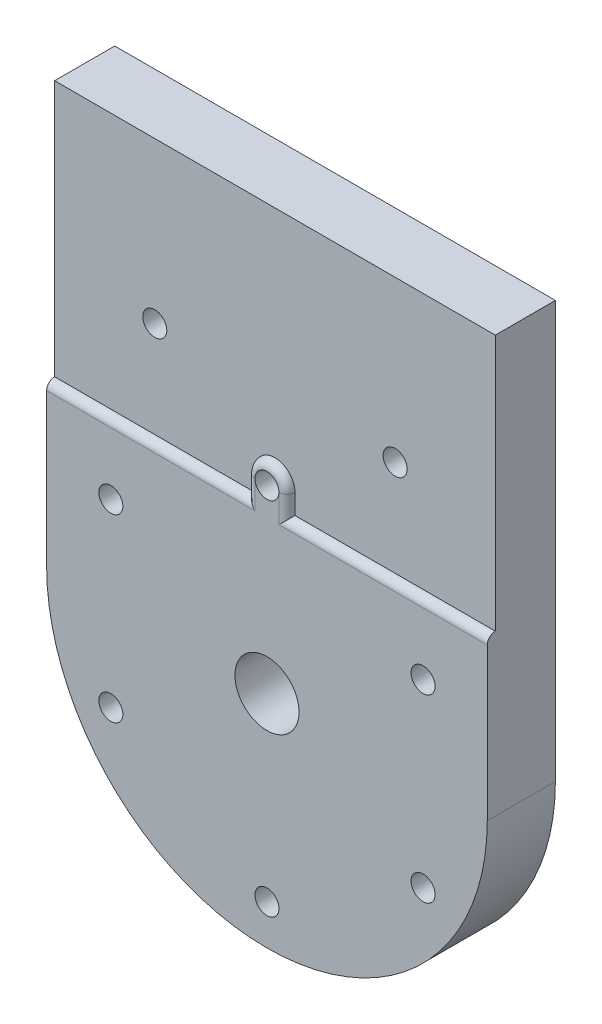
SolidWorks part; units mm, degrees
ref_plane "Plan de face" through (0, 0, 0) normal (0, 0, 1) x (1, 0, 0)
ref_plane "Plan de dessus" through (0, 0, 0) normal (0, 1, 0) x (1, 0, 0)
ref_plane "Plan de droite" through (0, 0, 0) normal (1, 0, 0) x (0, 0, -1)
sketch "Esquisse1" plane through (0, 0, 0) normal (0, 0, 1) x (1, 0, 0)
  line L0 (-50, 52) -> (50, 52)
  line L1 (-50, 52) -> (-50, -48.5481)
  line L2 (50, 52) -> (50, -48.5481)
  line L3 (-50, -48.5481) -> (50, -48.5481)
  circle A1 centre (0, 0) radius 4
  dimension "D1" = 52
extrude "Boss.-Extru.1" add sketch "Esquisse1" along normal blind 8.5
sketch "Esquisse2" plane through (0, 0, 8.5) normal (0, 0, 1) x (1, 0, 0)
  line L0 (-27.5, 0) -> (27.5, 0)
  line L1 (-27.5, 0) -> (-27.5, 55)
  line L2 (27.5, 0) -> (27.5, 55)
  line L3 (-27.5, 55) -> (27.5, 55)
  line L4 (-50, 52) -> (50, 52) construction
  circle A0 centre (0, 22.5) radius 1.5
  circle A1 centre (19.4856, 11.25) radius 1.5
  circle A2 centre (19.4856, -11.25) radius 1.5
  circle A3 centre (0, -22.5) radius 1.5
  circle A4 centre (-19.4856, -11.25) radius 1.5
  circle A5 centre (-19.4856, 11.25) radius 1.5
  circle A6 centre (0, 0) radius 27.5
  circle A13 centre (-15, 32) radius 1.5
  circle A14 centre (15, 32) radius 1.5
  point P4 (0, 0)
  point P12 (0, 0)
  point P32 (0, 0)
  point P33 (0, 0)
  dimension "D1" = 22.5
  dimension "D3" = 55
  dimension "D4" = 55
  dimension "D8" = 12.5
  dimension "D9" = 12.5
  dimension "D10" = 20
  dimension "D11" = 20
  dimension "D2" = 6
extrude "Enlèv. mat.-Extru.1" cut sketch "Esquisse2" against normal through all
sketch "Esquisse3" plane through (0, 0, 8.5) normal (0, 0, 1) x (1, 0, 0)
  line L0 (-27.5, 52) -> (27.5, 52)
  line L1 (-27.5, 52) -> (-27.5, 20)
  line L2 (27.5, 52) -> (27.5, 20)
  line L3 (-27.5, 20) -> (27.5, 20)
  line L4 (-2.5, 20) -> (2.5, 20)
  line L5 (-2.5, 20) -> (-2.5, 22.5)
  line L6 (2.5, 20) -> (2.5, 22.5)
  line L7 (-2.5, 22.5) -> (2.5, 22.5)
  circle A0 centre (0, 22.5) radius 2.5
  circle M14 centre (-15, 32) radius 1.5
  circle M15 centre (15, 32) radius 1.5
  line M18 (27.5, 0) -> (27.5, 52)
  line M19 (27.5, 52) -> (-27.5, 52)
  line M20 (-27.5, 52) -> (-27.5, 0)
  dimension "D1" = 32
  dimension "D2" = 5
  dimension "D3" = 2.5
  dimension "D4" = 25
extrude "Enlèv. mat.-Extru.6" cut sketch "Esquisse3" against normal blind 1 contours L5 L7 L6 L3 M18 M19 M20 M15 M14
fillet "Congé4" radius 1 5 edges at (-15, 20, 8.5) (15, 20, 8.5) (2.5, 21.25, 8.5) (-2.5, 21.25, 8.5) (0, 25, 8.5)
sketch "Esquisse4" plane through (0, 0, 0) normal (0, 0, -1) x (-1, 0, 0)
  circle A0 centre (0, 22.5) radius 3
  circle A1 centre (19.4856, 11.25) radius 3
  circle A2 centre (19.4856, -11.25) radius 3
  circle A3 centre (0, -22.5) radius 3
  circle A4 centre (-19.4856, -11.25) radius 3
  circle A5 centre (-19.4856, 11.25) radius 3
  point P15 (0, 0)
  dimension "D1" = 6
extrude "Enlèv. mat.-Extru.7" cut sketch "Esquisse4" against normal blind 4
